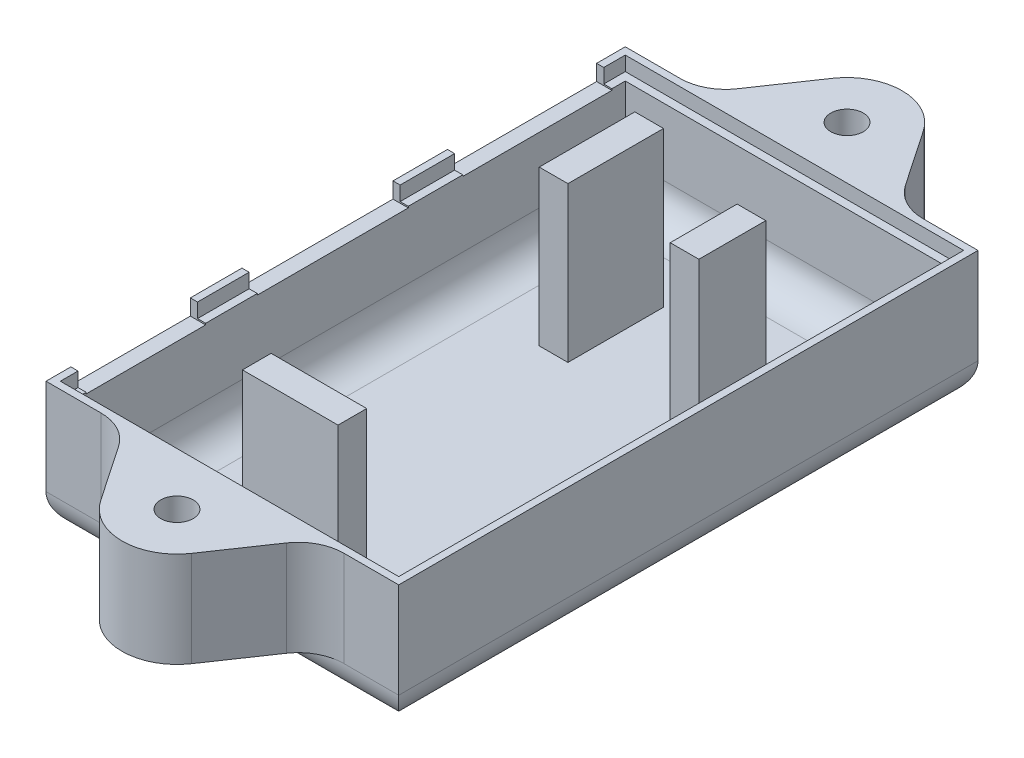
SolidWorks part; units mm, degrees
ref_plane "Спереди" through (0, 0, 0) normal (0, 0, 1) x (1, 0, 0)
ref_plane "Сверху" through (0, 0, 0) normal (0, 1, 0) x (1, 0, 0)
ref_plane "Справа" through (0, 0, 0) normal (1, 0, 0) x (0, 0, -1)
sketch "Эскиз1" plane through (0, 0, 0) normal (0, 1, 0) x (1, 0, 0)
  line L0 (347.1851, 1631.4336) -> (1749.4233, 1631.4336) construction
  line L2 (0, 0) -> (33.3, 0)
  line L3 (0, 0) -> (0, 57)
  line L4 (0, 57) -> (33.3, 57)
  line L5 (33.3, 0) -> (33.3, 57)
  circle A0 centre (5.1, 19.73) radius 0.75
  circle A1 centre (5.1, 41.13) radius 0.75
  circle A2 centre (23.55, 45) radius 0.75
  circle A3 centre (30.75, 12.6) radius 0.75
  dimension "D3" = 1.5
  dimension "D1" = 57
  dimension "D2" = 33.3
  dimension "D4" = 5.1
  dimension "D5" = 19.73
  dimension "D6" = 21.4
  dimension "D7" = 2.55
  dimension "D8" = 12.6
  dimension "D9" = 9.75
  dimension "D10" = 12
sketch "Эскиз2" plane through (0, 0, 0) normal (0, 1, 0) x (1, 0, 0)
  line L0 (0, 57) -> (33.3, 57) construction
  line L1 (33.3, 0) -> (33.3, 57) construction
  line L2 (0, 0) -> (33.3, 0) construction
  line L3 (0, 0) -> (0, 57) construction
  line L4 (0, 57) -> (33.3, 57) construction
  line L5 (33.3, 0) -> (33.3, 57) construction
  line L6 (0, 0) -> (33.3, 0) construction
  line L7 (0, 0) -> (0, 57) construction
  line L12 (-0.2, -0.2) -> (-0.2, 57.2)
  line L13 (-0.2, 57.2) -> (33.5, 57.2)
  line L14 (33.5, -0.2) -> (33.5, 57.2)
  line L15 (-0.2, -0.2) -> (33.5, -0.2)
  line L16 (-1.8, -1.8) -> (-1.8, 58.8)
  line L17 (-1.8, 58.8) -> (35.1, 58.8)
  line L18 (35.1, -1.8) -> (35.1, 58.8)
  line L19 (-1.8, -1.8) -> (35.1, -1.8)
  line L20 (-1.05, -1.05) -> (-1.05, 58.05)
  line L21 (-1.05, 58.05) -> (34.35, 58.05)
  line L22 (34.35, -1.05) -> (34.35, 58.05)
  line L23 (-1.05, -1.05) -> (34.35, -1.05)
  line L24 (16.65, 58.8) -> (16.65, -49941.2) construction
  line L25 (35.1, 28.5) -> (-49964.9, 28.5) construction
  line L26 (3.95, 69.3) -> (29.35, 69.3)
  line L27 (-1.8, 58.8) -> (-1.8, 63.55)
  line L28 (35.1, 58.8) -> (35.1, 63.55)
  line L29 (3.95, -12.3) -> (29.35, -12.3)
  line L30 (-1.8, -1.8) -> (-1.8, -6.55)
  line L31 (35.1, -1.8) -> (35.1, -6.55)
  line L32 (3.95, -1.8) -> (3.95, -12.3) construction
  line L39 (-1.8, -6.55) -> (35.1, -6.55) construction
  line L40 (29.35, -12.3) -> (29.35, -1.8) construction
  line L41 (7.8772, -3.8779) -> (11.8961, -9.7846)
  line L42 (25.4228, -3.8779) -> (21.4039, -9.7846)
  line L43 (25.4228, 60.8779) -> (21.4039, 66.7846)
  line L44 (7.8772, 60.8779) -> (11.8961, 66.7846)
  circle A0 centre (5.1, 19.73) radius 0.75 construction
  circle A1 centre (30.75, 12.6) radius 0.75 construction
  circle A2 centre (23.55, 45) radius 0.75 construction
  circle A3 centre (5.1, 41.13) radius 0.75 construction
  circle A4 centre (5.1, 19.73) radius 0.75
  circle A5 centre (30.75, 12.6) radius 0.75
  circle A6 centre (23.55, 45) radius 0.75
  circle A7 centre (5.1, 41.13) radius 0.75
  circle A8 centre (5.1, 41.13) radius 2.25
  circle A9 centre (23.55, 45) radius 2.25
  circle A10 centre (30.75, 12.6) radius 2.25
  circle A11 centre (5.1, 19.73) radius 2.25
  circle A12 centre (5.1, 41.13) radius 3.75
  circle A13 centre (23.55, 45) radius 3.75
  circle A14 centre (5.1, 19.73) radius 3.75
  arc A16 (33.5, 15.1495) -> (33.5, 10.0505) centre (30.75, 12.6) ccw
  circle A17 centre (16.65, 63.55) radius 1.6
  circle A18 centre (16.65, 63.55) radius 3
  circle A19 centre (3.95, 63.55) radius 2.1
  circle A20 centre (3.95, 63.55) radius 3.75
  circle A21 centre (29.35, 63.55) radius 3.75
  circle A22 centre (29.35, 63.55) radius 2.1
  arc A23 (-1.8, 63.55) -> (3.95, 69.3) centre (3.95, 63.55) cw
  arc A24 (29.35, 69.3) -> (35.1, 63.55) centre (29.35, 63.55) cw
  circle A25 centre (29.35, -6.55) radius 2.1
  circle A26 centre (29.35, -6.55) radius 3.75
  circle A27 centre (16.65, -6.55) radius 1.6
  circle A28 centre (16.65, -6.55) radius 3
  circle A29 centre (3.95, -6.55) radius 3.75
  circle A30 centre (3.95, -6.55) radius 2.1
  arc A31 (-1.8, -6.55) -> (3.95, -12.3) centre (3.95, -6.55) ccw
  arc A32 (29.35, -12.3) -> (35.1, -6.55) centre (29.35, -6.55) ccw
  arc A36 (11.8961, -9.7846) -> (21.4039, -9.7846) centre (16.65, -6.55) ccw
  arc A37 (7.8772, -3.8779) -> (3.95, -1.8) centre (3.95, -6.55) ccw
  arc A39 (29.35, -1.8) -> (25.4228, -3.8779) centre (29.35, -6.55) ccw
  arc A40 (11.8961, 66.7846) -> (21.4039, 66.7846) centre (16.65, 63.55) cw
  arc A41 (3.95, 58.8) -> (7.8772, 60.8779) centre (3.95, 63.55) ccw
  arc A42 (25.4228, 60.8779) -> (29.35, 58.8) centre (29.35, 63.55) ccw
  point P30 (30.75, 12.6)
  point P32 (34.5, 12.6)
  point P44 (16.65, 58.8)
  point P47 (35.1, 28.5)
  point P59 (16.65, 69.3)
  dimension "D1" = 4.5
  dimension "D7" = 3.2
  dimension "D8" = 6
  dimension "D10" = 4.2
  dimension "D11" = 7.5
  dimension "D12" = 1
  dimension "D13" = 2
  dimension "D14" = 2
  dimension "D2" = 1.6
  dimension "D3" = 1.5
  dimension "D4" = 1.5
  dimension "D5" = 0.2
  dimension "D6" = 0.75
extrude "Бобышка-Вытянуть1" add sketch "Эскиз2" along normal blind 1.5 contours A5 | A10 A5 | L14 A16 A10 | A4 | A11 A4 | A14 A11 | A7 | A8 A7 | A12 A8 | A6 | A9 A6 | A13 A9 | A16 L14 L13 L12 L15 A14 A13 A12 | L16 L19 L18 L17 L15 L12 L13 L14 | L20 L23 L22 L21 L15 L12 L13 L14 region at (16.737, 0, -28.3565) region at (27.0992, 0, -12.6) region at (-1.0905, 0, -28.5) region at (-0.3611, 0, -28.5) region at (5.1, 0, -19.73) region at (30.75, 0, -12.6) region at (23.55, 0, -45) region at (5.1, 0, -41.13) region at (2.9136, 0, -41.13) region at (21.3636, 0, -45) region at (28.5636, 0, -12.6) region at (2.9136, 0, -19.73) region at (1.4561, 0, -41.13) region at (19.9061, 0, -45) region at (1.4561, 0, -19.73)
extrude "Бобышка-Вытянуть9" add sketch "Эскиз2<20>" along normal blind 12 from surface contours L16 L19 L18 L17 L23 L20 L21 L22 | L20 L23 L22 L21 L15 L12 L13 L14 region at (-1.0905, 0, -28.5) region at (-0.3611, 0, -28.5) starting at face at (16.65, 1.5, -28.5)
sketch "Эскиз2<20>" plane through (0, 0, 0) normal (0, 1, 0) x (1, 0, 0) same geometry as "Эскиз2"
extrude "Вырез-Вытянуть3" cut sketch "Эскиз2<21>" against normal blind 1.5 from surface contours L20 L23 L22 L21 L15 L12 L13 L14 region at (-0.3611, 0, -28.5) starting at face at (16.65, 13.5, -28.5)
sketch "Эскиз2<21>" plane through (0, 0, 0) normal (0, 1, 0) x (1, 0, 0) same geometry as "Эскиз2"
extrude "Бобышка-Вытянуть10" add sketch "Эскиз2<23>" against normal blind 10 from surface contours A42 L43 A40 L44 A41 L17 A18 | A18 A17 | A39 L19 A37 L41 A36 L42 A28 | A28 A27 region at (16.65, 0, 2.0748) region at (6.3001, 0, -59.1086) region at (13.7349, 0, -63.55) region at (13.7349, 0, 6.55) starting at face at (16.65, 13.5, -28.5)
sketch "Эскиз2<23>" plane through (0, 0, 0) normal (0, 1, 0) x (1, 0, 0) same geometry as "Эскиз2"
fillet "Скругление2" radius 3.5 8 edges at (-1.8, 0, -28.5) (16.65, 0, -58.8) (35.1, 0, -28.5) (16.65, 0, 1.8) (16.65, 1.5, -57.2) (-0.2, 1.5, -28.5) (16.65, 1.5, 0.2) (33.5, 1.5, -28.5)
hole_wizard "Зенковка для  винта с потайной головкой с внутренним шестигранником M32" positions "Эскиз10" profile "Эскиз11" countersink size "M3" standard "Ansi Metric" end condition through all
sketch "Эскиз10" plane through (0, 3.5, 0) normal (0, -1, 0) x (-1, 0, 0)
  point P0 (-16.65, 63.55)
  point P3 (-16.65, -6.55)
sketch "Эскиз11" plane through (16.65, 3.5, -63.55) normal (1, 0, 0) x (0, 0, -1)
  line L0 (0, 0) -> (0, 10)
  line L1 (0, 10) -> (1.7, 10)
  line L2 (1.7, 10) -> (1.7, 1.66)
  line L3 (1.7, 1.66) -> (3.36, 0)
  line L5 (3.36, 0) -> (0, 0)
  line L6 (-1.7, 1.66) -> (-3.36, 0) construction
  line L11 (0, -6.35) -> (0, 107.95) construction
  dimension "Диаметр сквозного отверстия" = 3.4
  dimension "Глубина сквозного отверстия" = 10
  dimension "Диаметр передней зенковки" = 6.72
  dimension "Угол передней зенковки" = 90
sketch "Эскиз12" plane through (0, 13.5, 0) normal (0, 1, 0) x (1, 0, 0)
  line L0 (-1.8, 55.8) -> (-0.2, 55.8)
  line L1 (-1.8, 58.8) -> (-1.8, -1.8) construction
  line L2 (-0.2, -0.2) -> (-0.2, 57.2) construction
  line L3 (-0.2, 57.2) -> (33.5, 57.2) construction
  line L4 (-1.8, 40.2) -> (-0.2, 40.2)
  line L6 (-0.2, 57.2) -> (-0.2, -0.2) construction
  line L7 (-1.8, 34.5) -> (-0.2, 34.5)
  line L8 (-1.8, 0.8) -> (-0.2, 0.8)
  line L9 (33.5, -0.2) -> (-0.2, -0.2) construction
  line L10 (-1.8, 13.3) -> (-0.2, 13.3)
  line L11 (-1.8, 18.7) -> (-0.2, 18.7)
  line L12 (-1.8, 13.3) -> (-1.8, 0.8)
  line L13 (-0.2, 13.3) -> (-0.2, 0.8)
  line L14 (-1.8, 34.5) -> (-1.8, 18.7)
  line L15 (-0.2, 34.5) -> (-0.2, 18.7)
  line L16 (-1.8, 55.8) -> (-1.8, 40.2)
  line L17 (-0.2, 55.8) -> (-0.2, 40.2)
  dimension "D1" = 1.4
  dimension "D2" = 15.6
  dimension "D3" = 5.7
  dimension "D4" = 1
  dimension "D5" = 5.4
  dimension "D6" = 12.5
extrude "Вырез-Вытянуть4" cut sketch "Эскиз12" against normal blind 1.65
sketch "Эскиз13" plane through (0, 1.5, 0) normal (0, 1, 0) x (1, 0, 0)
  line L5 (16.65, 63.55) -> (16.65, -49936.45) construction
  line L8 (-0.2, -0.2) -> (33.5, -0.2) construction
  line L9 (8.8, 49.2) -> (11.8, 49.2)
  line L10 (8.8, 49.2) -> (8.8, 39.2)
  line L11 (8.8, 39.2) -> (11.8, 39.2)
  line L12 (11.8, 49.2) -> (11.8, 39.2)
  line L13 (22.5, 46.2) -> (25.5, 46.2)
  line L14 (22.5, 46.2) -> (22.5, 39.2)
  line L15 (22.5, 39.2) -> (25.5, 39.2)
  line L16 (25.5, 46.2) -> (25.5, 39.2)
  line L17 (11.65, 8.3) -> (21.65, 8.3)
  line L18 (11.65, 8.3) -> (11.65, 5.3)
  line L19 (11.65, 5.3) -> (21.65, 5.3)
  line L20 (21.65, 8.3) -> (21.65, 5.3)
  line L21 (-0.2, 57.2) -> (33.5, 57.2) construction
  line L22 (-0.2, 40.2) -> (-0.2, 55.8) construction
  line L23 (33.5, -0.2) -> (33.5, 57.2) construction
  point P0 (16.65, 5.3)
  point P1 (21.65, 6.8)
  point P19 (23.6372, 40.6552)
  point P20 (23.3768, 50.3786)
  point P21 (12.5477, 39.6471)
  point P24 (11.7695, 54.6926)
  point P25 (11.9857, 39.2)
  point P28 (22.2232, 46.5201)
  dimension "D1" = 3
  dimension "D2" = 10
  dimension "D3" = 7
  dimension "D4" = 18
  dimension "D5" = 10
  dimension "D6" = 9
  dimension "D7" = 7
  dimension "D8" = 8
extrude "Бобышка-Вытянуть11" add sketch "Эскиз13" along normal blind 16.2
